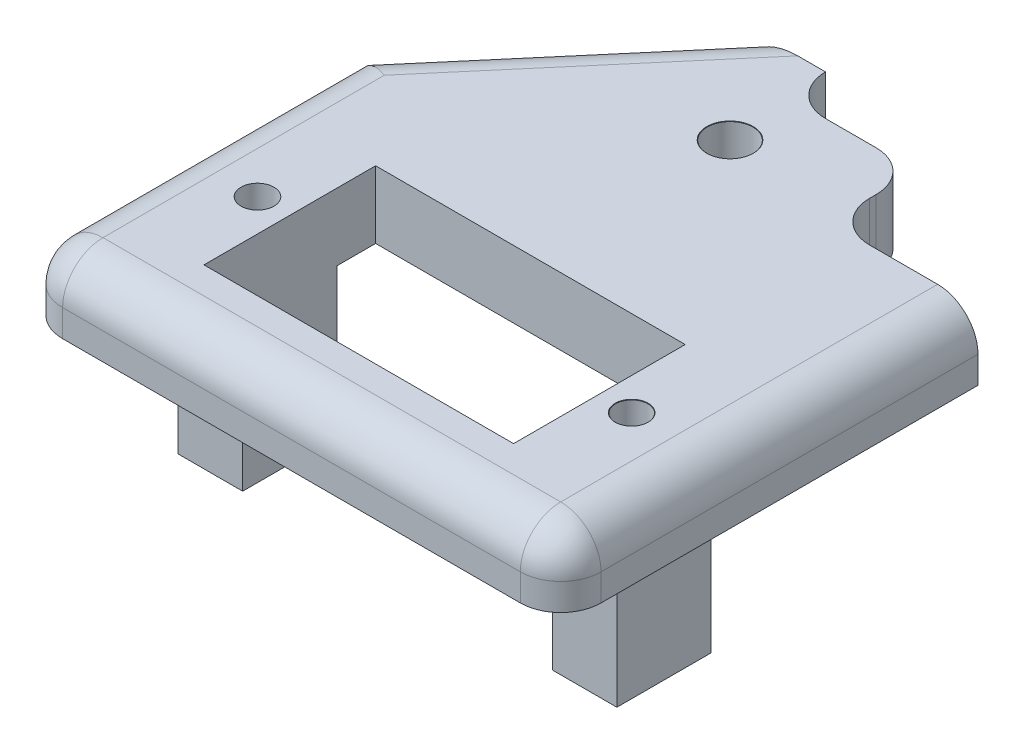
SolidWorks part; units mm, degrees
ref_plane "Front Plane" through (0, 0, 0) normal (0, 0, 1) x (1, 0, 0)
ref_plane "Top Plane" through (0, 0, 0) normal (0, 1, 0) x (1, 0, 0)
ref_plane "Right Plane" through (0, 0, 0) normal (1, 0, 0) x (0, 0, -1)
sketch "Sketch1" plane through (0, 0, 0) normal (0, 1, 0) x (1, 0, 0)
  line L0 (-3, 0) -> (-9, 0)
  line L5 (0, -3) -> (3.77, -3)
  line L6 (6.77, -6) -> (6.77, -6.5)
  line L7 (9.77, -6.5) -> (6.77, -6.5) construction
  line L8 (9.77, -9.5) -> (9.77, -15.5)
  line L9 (-9, 0) -> (-9, -15.5)
  line L10 (-9, -15.5) -> (9.77, -15.5)
  arc A0 (-3, 0) -> (0, -3) centre (0, 0) ccw
  arc A1 (6.77, -6) -> (3.77, -3) centre (3.77, -6) ccw
  arc A2 (6.77, -6.5) -> (9.77, -9.5) centre (9.77, -6.5) ccw
  dimension "D1" = 6
  dimension "D2" = 6
  dimension "D3" = 0.5
  dimension "D4" = 3.77
extrude "Boss-Extrude1" add sketch "Sketch1" along normal blind 5 contours L9 L10 L8 A2 L6 A1 L5 A0 L0
hole_wizard "M3 Clearance Hole1" positions "Sketch2" profile "Sketch3" hole size "M3" standard "ANSI Metric" end condition through all
sketch "Sketch2" plane through (0, 5, 0) normal (0, 1, 0) x (1, 0, 0)
  line L1 (-2.1713, -7.9213) -> (-2.1213, -7.9213) construction
  line L2 (-2.1213, -7.9213) -> (-2.1213, -2.1213) construction
  arc A1 (-3, 0) -> (0, -3) centre (0, 0) ccw construction
  point P0 (-2.1713, -7.9213)
  dimension "D1" = 5.8
  dimension "D2" = 0.05
sketch "Sketch3" plane through (-2.1713, 5, 7.9213) normal (1, 0, 0) x (0, 0, 1)
  line L0 (0, 0) -> (0, 5)
  line L1 (0, 5) -> (1.7, 5)
  line L2 (1.7, 5) -> (1.7, 0.025)
  line L3 (1.7, 0.025) -> (1.725, 0)
  line L5 (1.725, 0) -> (0, 0)
  line L6 (-1.7, 0.025) -> (-1.725, 0) construction
  line L11 (0, -6.35) -> (0, 107.95) construction
  dimension "Thru Hole Dia." = 3.4
  dimension "Thru Hole Depth" = 5
  dimension "Near C'Sink Dia." = 3.45
  dimension "Near C'Sink Angle" = 90
sketch "Sketch4" plane through (0, 5, 0) normal (0, 1, 0) x (1, 0, 0)
  line L0 (-9, -15.5) -> (9.77, -15.5) construction
  line L1 (-22.1713, -15.5) -> (17.8287, -15.5)
  line L2 (-22.1713, -15.5) -> (-22.1713, -40.5)
  line L3 (-22.1713, -40.5) -> (17.8287, -40.5)
  line L4 (17.8287, -40.5) -> (17.8287, -15.5)
  circle A0 centre (-2.1713, -7.9213) radius 1.725 construction
  circle A1 centre (-2.1713, -7.9213) radius 1.725 construction
  point P10 (-2.1713, -15.5)
  dimension "D1" = 40
  dimension "D2" = 25
extrude "Boss-Extrude2" add sketch "Sketch4" against normal up to surface (5 mm away) up to face at (-2.1713, 0, 9.6213)
sketch "Sketch5" plane through (0, 5, 0) normal (0, 1, 0) x (1, 0, 0)
  line L0 (17.8287, -15.5) -> (9.77, -15.5) construction
  line L1 (9.77, -9.5) -> (9.77, -15.5) construction
  line L2 (17.8287, -15.5) -> (9.77, -15.5)
  line L3 (9.77, -9.5) -> (9.77, -15.5)
  line L4 (9.77, -9.5) -> (17.8287, -9.5)
  line L5 (17.8287, -9.5) -> (17.8287, -15.5)
  line L6 (-9, -15.5) -> (-22.1713, -15.5) construction
  line L7 (-9, 0) -> (-9, -15.5) construction
  line L8 (-9, -15.5) -> (-22.1713, -15.5)
  line L9 (-9, 0) -> (-9, -15.5)
  line L12 (-22.1713, -15.5) -> (-9, 0)
extrude "Boss-Extrude3" add sketch "Sketch5" against normal up to surface (5 mm away) up to face at (-2.1713, 0, 9.6213)
sketch "Sketch8" plane through (0, 5, 0) normal (0, 1, 0) x (1, 0, 0)
  line L0 (-22.1713, -15.5) -> (17.8287, -15.5) construction
  line L1 (17.8287, -40.5) -> (17.8287, -9.5) construction
  line L2 (-2.1713, -29.125) -> (-2.1713, -7.9213) construction
  line L3 (-13.6713, -22.75) -> (9.3287, -22.75)
  line L4 (-13.6713, -22.75) -> (-13.6713, -35.5)
  line L5 (-13.6713, -35.5) -> (9.3287, -35.5)
  line L6 (9.3287, -22.75) -> (9.3287, -35.5)
  line L7 (-13.6713, -22.75) -> (9.3287, -35.5) construction
  line L8 (-13.6713, -35.5) -> (9.3287, -22.75) construction
  line L9 (-22.1713, -40.5) -> (17.8287, -40.5) construction
  circle A1 centre (-2.1713, -7.9213) radius 1.725 construction
  circle A2 centre (-2.1713, -7.9213) radius 1.725 construction
  point P5 (-2.1713, -29.125)
  dimension "D1" = 23
  dimension "D2" = 12.75
  dimension "D3" = 5
extrude "Cut-Extrude1" cut sketch "Sketch8" against normal up to surface (5 mm away) contours L4 L5 L6 L3 up to face at (-2.1713, 0, 9.6213)
hole_wizard "M2 Clearance Hole1" positions "Sketch9" profile "Sketch10" hole size "M2" standard "ANSI Metric" end condition through all
sketch "Sketch9" plane through (0, 5, 0) normal (0, 1, 0) x (1, 0, 0)
  line L0 (-16.0713, -29.125) -> (11.7287, -29.125) construction
  line L1 (-2.1713, -29.125) -> (-2.1713, -22.75) construction
  line L2 (-13.6713, -22.75) -> (9.3287, -22.75) construction
  line L3 (-2.1713, -29.125) -> (-2.1713, -35.5) construction
  line L4 (-13.6713, -35.5) -> (9.3287, -35.5) construction
  line L5 (-22.1713, -15.5) -> (17.8287, -15.5) construction
  line L6 (17.8287, -40.5) -> (17.8287, -9.5) construction
  point P0 (-16.0713, -29.125)
  point P2 (11.7287, -29.125)
  dimension "D1" = 27.8
sketch "Sketch10" plane through (-16.0713, 5, 29.125) normal (1, 0, 0) x (0, 0, 1)
  line L0 (0, 0) -> (0, 5)
  line L1 (0, 5) -> (1.2, 5)
  line L2 (1.2, 5) -> (1.2, 0.025)
  line L3 (1.2, 0.025) -> (1.225, 0)
  line L5 (1.225, 0) -> (0, 0)
  line L6 (-1.2, 0.025) -> (-1.225, 0) construction
  line L11 (0, -6.35) -> (0, 107.95) construction
  dimension "Thru Hole Dia." = 2.4
  dimension "Thru Hole Depth" = 5
  dimension "Near C'Sink Dia." = 2.45
  dimension "Near C'Sink Angle" = 90
fillet "Fillet1" radius 3 6 edges at (-22.1713, 2.5, 40.5) (17.8287, 2.5, 40.5) (-2.1713, 5, 40.5) (17.8287, 5, 25) (-22.1713, 5, 28) (-15.5857, 5, 7.75)
sketch "Sketch11" plane through (0, 0, 0) normal (0, -1, 0) x (1, 0, 0)
  line L0 (-13.6713, 35.5) -> (-13.6713, 22.75) construction
  line L1 (-13.6713, 32.625) -> (-18.4713, 32.625)
  line L2 (-13.6713, 32.625) -> (-13.6713, 25.625)
  line L3 (-13.6713, 25.625) -> (-18.4713, 25.625)
  line L4 (-18.4713, 32.625) -> (-18.4713, 25.625)
  line L5 (-13.6713, 32.625) -> (-18.4713, 25.625) construction
  line L6 (-13.6713, 25.625) -> (-18.4713, 32.625) construction
  line L7 (14.1287, 32.625) -> (9.3287, 32.625)
  line L8 (14.1287, 32.625) -> (14.1287, 25.625)
  line L9 (14.1287, 25.625) -> (9.3287, 25.625)
  line L10 (9.3287, 32.625) -> (9.3287, 25.625)
  line L11 (14.1287, 32.625) -> (9.3287, 25.625) construction
  line L12 (14.1287, 25.625) -> (9.3287, 32.625) construction
  point P0 (-16.0713, 29.125)
  point P6 (11.7287, 29.125)
  dimension "D1" = 7
extrude "Boss-Extrude4" add sketch "Sketch11" along normal blind 11
sketch "Sketch12" plane through (0, -11, 0) normal (0, -1, 0) x (1, 0, 0)
  line L1 (-16.0713, 26.7001) -> (-13.9713, 27.9126)
  line L2 (-13.9713, 27.9126) -> (-13.9713, 30.3374)
  line L3 (-13.9713, 30.3374) -> (-16.0713, 31.5499)
  line L4 (-16.0713, 31.5499) -> (-18.1713, 30.3374)
  line L5 (-18.1713, 30.3374) -> (-18.1713, 27.9126)
  line L6 (-18.1713, 27.9126) -> (-16.0713, 26.7001)
  line L7 (11.7287, 26.7001) -> (13.8287, 27.9126)
  line L8 (13.8287, 27.9126) -> (13.8287, 30.3374)
  line L9 (13.8287, 30.3374) -> (11.7287, 31.5499)
  line L10 (11.7287, 31.5499) -> (9.6287, 30.3374)
  line L11 (9.6287, 30.3374) -> (9.6287, 27.9126)
  line L12 (9.6287, 27.9126) -> (11.7287, 26.7001)
  circle A0 centre (11.7287, 29.125) radius 1.2 construction
  circle A1 centre (-16.0713, 29.125) radius 1.2 construction
  circle A2 centre (11.7287, 29.125) radius 1.2 construction
  circle A3 centre (-16.0713, 29.125) radius 1.2 construction
  circle A4 centre (-16.0713, 29.125) radius 2.1 construction
  circle A5 centre (11.7287, 29.125) radius 2.1 construction
  dimension "D1" = 4.2
extrude "Cut-Extrude2" cut sketch "Sketch12" against normal blind 1.75
sketch "Sketch13" plane through (0, -9.25, 0) normal (0, -1, 0) x (1, 0, 0)
  circle A0 centre (-16.0713, 29.125) radius 1.225 construction
  circle A1 centre (11.7287, 29.125) radius 1.2 construction
  circle A2 centre (-16.0713, 29.125) radius 1.225
  circle A3 centre (11.7287, 29.125) radius 1.2
extrude "Cut-Extrude3" cut sketch "Sketch13" against normal up to surface (14.25 mm away) up to face at (-16.0713, 5, 30.35)
